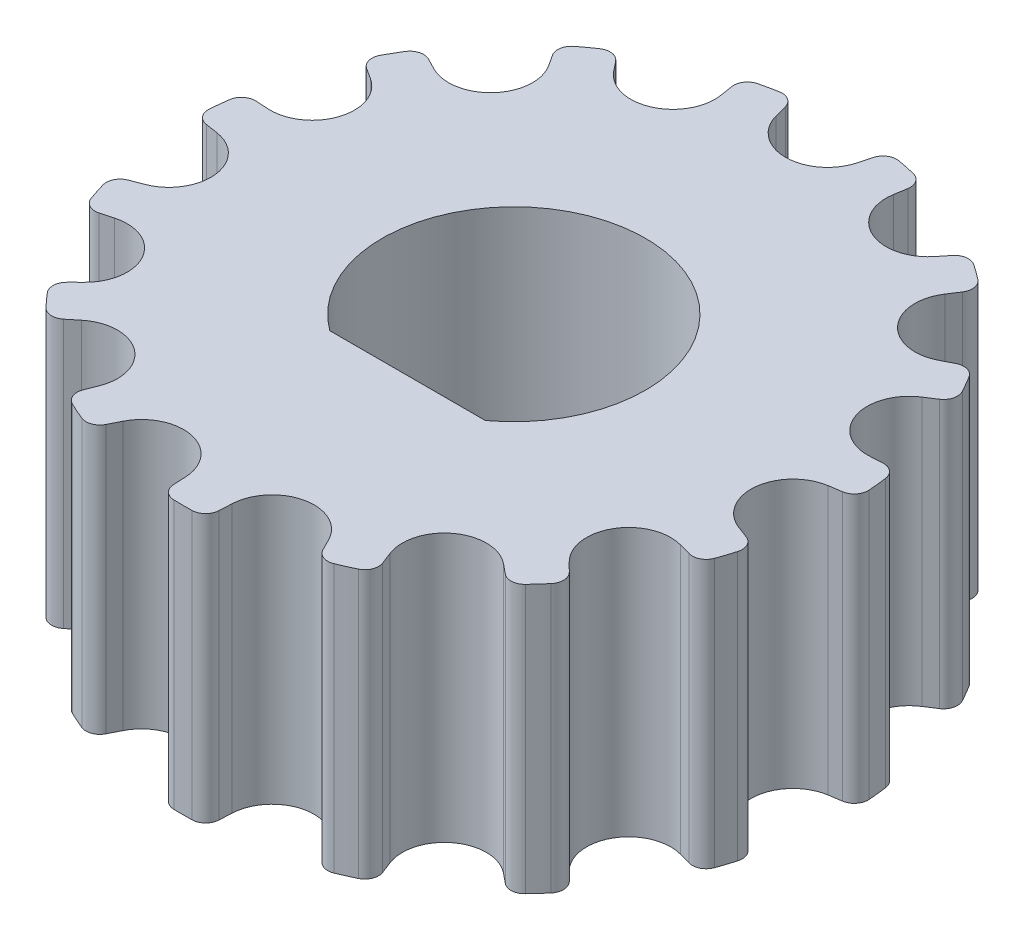
SolidWorks part; units mm, degrees
ref_plane "Front Plane" through (0, 0, 0) normal (0, 0, 1) x (1, 0, 0)
ref_plane "Top Plane" through (0, 0, 0) normal (0, 1, 0) x (1, 0, 0)
ref_plane "Right Plane" through (0, 0, 0) normal (1, 0, 0) x (0, 0, -1)
sketch "Sketch1" plane through (0, 0, 0) normal (0, 1, 0) x (1, 0, 0)
  circle A0 centre (0, 0) radius 7.162
  dimension "D1" = 14.3239
extrude "Boss-Extrude1" add sketch "Sketch1" along normal blind 5.8
sketch "Sketch2" plane through (0, 5.8, 0) normal (0, 1, 0) x (1, 0, 0)
  line L0 (0, 0) -> (0, 7.162) construction
  line L1 (-0.8799, 6.5598) -> (-0.95, 6.8255)
  line L2 (-2.913, 6.5428) -> (-2.913, 7.162)
  line L3 (-2.913, 7.162) -> (2.913, 7.162)
  line L4 (0.8799, 6.5598) -> (0.95, 6.8255)
  line L5 (2.913, 6.5428) -> (2.913, 7.162)
  circle A0 centre (0, 0) radius 7.162 construction
  arc A1 (0.8799, 6.5598) -> (-0.8799, 6.5598) centre (0, 6.792) cw
  arc A2 (-0.95, 6.8255) -> (-1.2943, 7.0441) centre (-1.2401, 6.749) ccw
  arc A4 (0.95, 6.8255) -> (1.2943, 7.0441) centre (1.2401, 6.749) cw
  arc A5 (-1.2943, 7.0441) -> (-2.913, 6.5428) centre (0, 0) ccw
  arc A6 (1.2943, 7.0441) -> (2.913, 6.5428) centre (0, 0) cw
  point P11 (0, 7.162)
  point P19 (0, 5.882)
  dimension "D3" = 0.3
  dimension "D5" = 0.91
  dimension "D2" = 0.95
  dimension "D4" = 1.28
  dimension "D6" = 24
extrude "Cut-Extrude1" cut sketch "Sketch2" against normal through all
pattern_circular "CirPattern1" count 15 over 360 about axis through (0, 5.8, 0) along (0, -1, 0) of "Cut-Extrude1"
sketch "Sketch3" plane through (0, 0, 0) normal (0, -1, 0) x (1, 0, 0)
  line L0 (1.683, 2.3) -> (-1.683, 2.3)
  arc A0 (-1.683, 2.3) -> (1.683, 2.3) centre (0, 0) ccw
  dimension "D1" = 5.7
  dimension "D2" = 2.3
extrude "Cut-Extrude2" cut sketch "Sketch3" against normal through all
equation "\"smallPulleyTeeth\"= 15"
equation "\"largePulleyTeeth\"= 30"
equation "\"eighthThick\"= 2.9mm"
equation "\"bushingDiam\"= 7.85mm"
equation "\"D1@Sketch1\"=3*\"smallPulleyTeeth\"/pi"
equation "\"D1@Boss-Extrude1\" = \"eighthThick\" * 2"
equation "\"D6@Sketch2\"=360/\"smallPulleyTeeth\""
equation "\"quarterThick\"=5.6mm"
equation "\"D1@CirPattern1\"=\"smallPulleyTeeth\""
